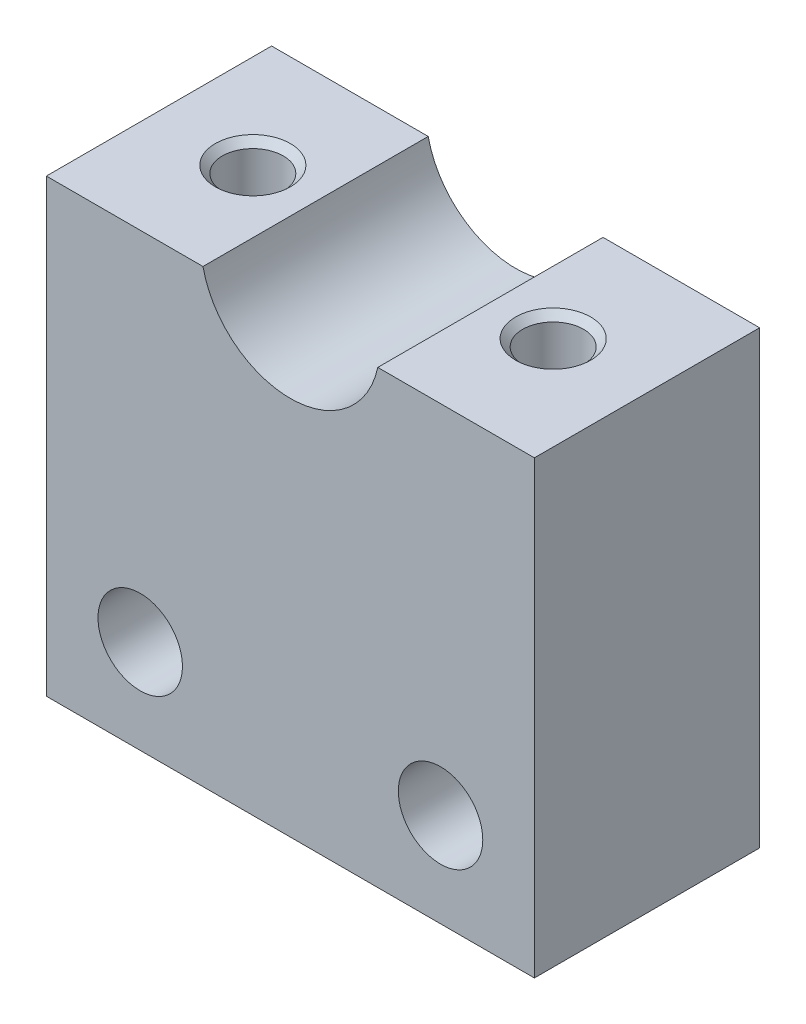
SolidWorks part; units mm, degrees
material "6061 Alloy"
ref_plane "Front Plane" through (0, 0, 0) normal (0, 0, 1) x (1, 0, 0)
ref_plane "Top Plane" through (0, 0, 0) normal (0, 1, 0) x (1, 0, 0)
ref_plane "Right Plane" through (0, 0, 0) normal (1, 0, 0) x (0, 0, -1)
ref_plane "Plane1" through (0, 0, 6) normal (0, 0, 1) x (1, 0, 0)
sketch "Sketch1" plane through (0, 0, 6) normal (0, 0, 1) x (1, 0, 0)
  line L0 (13, 24) -> (-13, 24)
  line L1 (-13, 24) -> (-13, 0)
  line L2 (-13, 0) -> (13, 0)
  line L3 (13, 0) -> (13, 24)
extrude "Boss-Extrude1" add sketch "Sketch1" against normal blind 12
sketch "Sketch2" plane through (0, 0, -6) normal (0, 0, -1) x (-1, 0, 0)
  line L0 (4.6563, 24) -> (-4.6563, 24)
  line L1 (-13, 24) -> (13, 24) construction
  arc A0 (-4.6563, 24) -> (4.6563, 24) centre (0, 25) ccw
  dimension "D1" = 4.7625
  dimension "D2" = 1
extrude "Cut-Extrude1" cut sketch "Sketch2" against normal through all
hole_wizard "M3 Clearance Hole1" positions "Sketch4" profile "Sketch3" hole size "M3" standard "ANSI Metric"
sketch "Sketch4" plane through (0, 24, 0) normal (0, 1, 0) x (1, 0, 0)
  point P0 (8, 0)
  point P1 (-8, 0)
sketch "Sketch3" plane through (8, 24, 0) normal (1, 0, 0) x (0, 0, 1)
  line L0 (0, 0) -> (0, 7)
  line L1 (0, 7) -> (1.621, 6.0641)
  line L2 (1.621, 6.0641) -> (1.621, 0)
  line L5 (1.621, 0) -> (0, 0)
  line L10 (0, 7) -> (-1.621, 6.0641) construction
  line L11 (0, -6.35) -> (0, 107.95) construction
  dimension "Hole Dia." = 3.242
  dimension "Hole Depth" = 6.0641
  dimension "Drill Angle" = 120
hole_wizard "Ø4.5 (4.5) Diameter Hole1" positions "Sketch6" profile "Sketch5" hole size "Ø4.5" standard "ANSI Metric"
sketch "Sketch6" plane through (0, 0, 6) normal (0, 0, 1) x (1, 0, 0)
  point P0 (8, 5)
  point P1 (-8, 5)
sketch "Sketch5" plane through (8, 5, 6) normal (1, 0, 0) x (0, -1, 0)
  line L0 (0, 0) -> (0, 12)
  line L1 (0, 12) -> (2.25, 12)
  line L2 (2.25, 12) -> (2.25, 0)
  line L5 (2.25, 0) -> (0, 0)
  line L11 (0, -6.35) -> (0, 107.95) construction
  dimension "Thru Hole Dia." = 4.5
  dimension "Thru Hole Depth" = 12
chamfer "Chamfer1" distance 0.379 angle 45 2 edges at (-8, 24, 1.621) (8, 24, 1.621)
